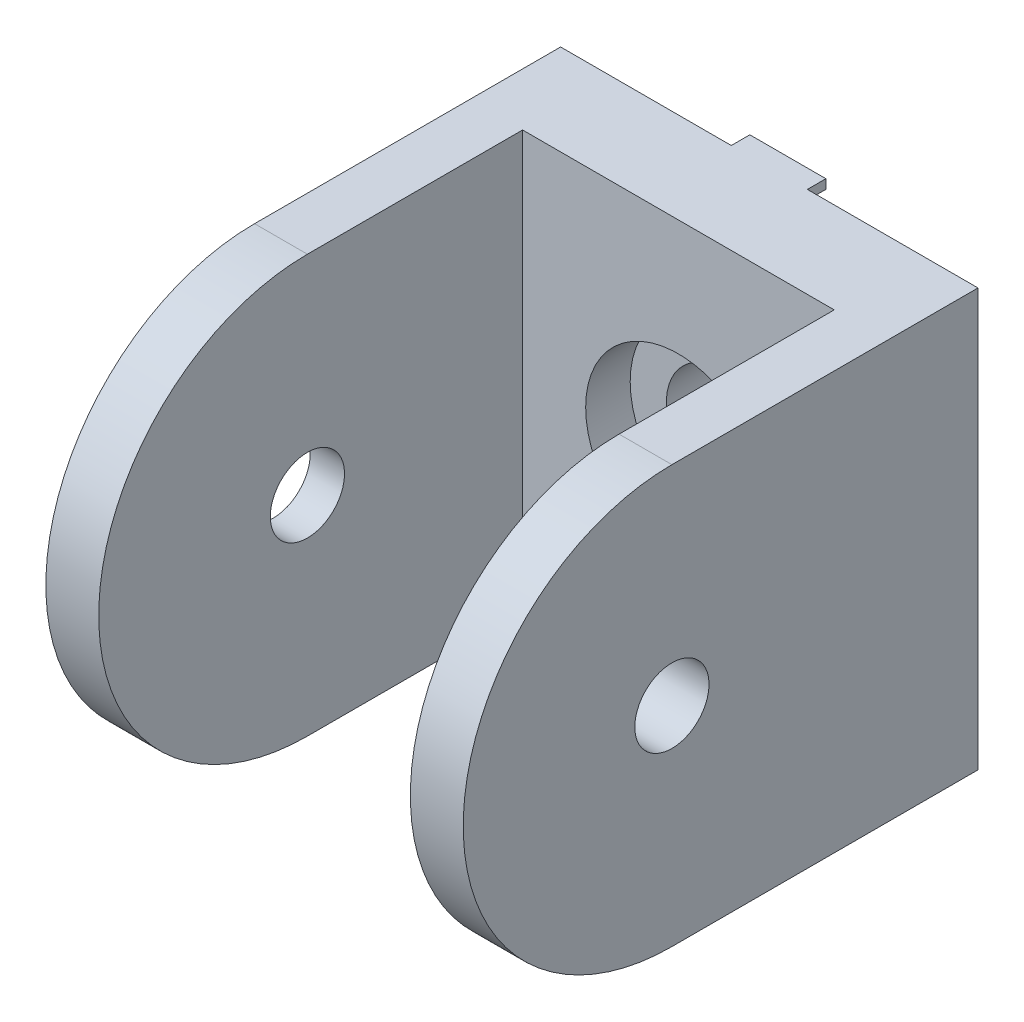
SolidWorks part; units mm, degrees
ref_plane "前视基准面" through (0, 0, 0) normal (0, 0, 1) x (1, 0, 0)
ref_plane "上视基准面" through (0, 0, 0) normal (0, 1, 0) x (1, 0, 0)
ref_plane "右视基准面" through (0, 0, 0) normal (1, 0, 0) x (0, 0, -1)
sketch "草图1" plane through (0, 0, 0) normal (0, 0, 1) x (1, 0, 0)
  line L1 (-22.5, -22.5) -> (22.5, -22.5)
  line L2 (-22.5, -22.5) -> (-22.5, 22.5)
  line L3 (-22.5, 22.5) -> (22.5, 22.5)
  line L4 (22.5, -22.5) -> (22.5, 22.5)
  line L5 (-22.5, -22.5) -> (22.5, 22.5) construction
  line L6 (-22.5, 22.5) -> (22.5, -22.5) construction
  point P0 (0, 0)
  dimension "D1" = 45
  dimension "D2" = 45
extrude "凸台-拉伸1" add sketch "草图1" along normal blind 9.8
sketch "草图2" plane through (0, 0, 9.8) normal (0, 0, 1) x (1, 0, 0)
  line L0 (22.5, 22.5) -> (-22.5, 22.5) construction
  line L1 (-22.5, -22.5) -> (-16.8, -22.5)
  line L2 (-22.5, -22.5) -> (-22.5, 22.5)
  line L3 (-22.5, 22.5) -> (-16.8, 22.5)
  line L4 (-16.8, -22.5) -> (-16.8, 22.5)
  line L5 (0, 0) -> (0, 12.8397) construction
  line L6 (22.5, -22.5) -> (16.8, -22.5)
  line L7 (22.5, -22.5) -> (22.5, 22.5)
  line L8 (16.8, -22.5) -> (16.8, 22.5)
  line L9 (22.5, 22.5) -> (16.8, 22.5)
  dimension "D1" = 5.7
extrude "凸台-拉伸2" add sketch "草图2" along normal blind 45.7
sketch "草图3" plane through (-22.5, 0, 0) normal (-1, 0, 0) x (0, 0, 1)
  line L0 (55.5, 22.5) -> (55.5, -22.5) construction
  line L1 (55.5, 22.5) -> (0, 22.5) construction
  line L2 (33, -22.5) -> (33, 22.5) construction
  arc A0 (33, -22.5) -> (33, 22.5) centre (33, 0) ccw
  dimension "D1" = 45
extrude "切除-拉伸2" cut sketch "草图3" against normal through all and the other way through all flip side to cut
sketch "草图4" plane through (-22.5, 0, 0) normal (-1, 0, 0) x (0, 0, 1)
  circle A0 centre (33, 0) radius 4
  dimension "D1" = 8
extrude "切除-拉伸3" cut sketch "草图4" against normal through all
sketch "草图5" plane through (-22.5, 0, 0) normal (-1, 0, 0) x (0, 0, 1)
  circle A0 centre (33, 0) radius 8
  dimension "D1" = 16
extrude "切除-拉伸4" cut sketch "草图5" against normal blind 2
sketch "草图6" plane through (0, 0, 9.8) normal (0, 0, 1) x (1, 0, 0)
  circle A0 centre (0, 0) radius 6.1
  dimension "D1" = 12.2
extrude "切除-拉伸5" cut sketch "草图6" against normal through all
sketch "草图7" plane through (0, 0, 0) normal (0, 0, -1) x (-1, 0, 0)
  line L0 (-22.5, 22.5) -> (22.5, 22.5) construction
  line L1 (-4.1, 22.5) -> (4.1, 22.5)
  line L2 (-4.1, 22.5) -> (-4.1, 21.5)
  line L3 (-4.1, 21.5) -> (4.1, 21.5)
  line L4 (4.1, 22.5) -> (4.1, 21.5)
  line L5 (0, 0) -> (-9.0525, 0) construction
  line L6 (4.1, -22.5) -> (4.1, -21.5)
  line L7 (-4.1, -22.5) -> (-4.1, -21.5)
  line L8 (-4.1, -21.5) -> (4.1, -21.5)
  line L9 (-4.1, -22.5) -> (4.1, -22.5)
  point P9 (0, 22.5)
  point P10 (0, 22.5)
  dimension "D1" = 8.2
  dimension "D2" = 1
extrude "凸台-拉伸3" add sketch "草图7" along normal blind 2
sketch "草图8" plane through (0, 0, 9.8) normal (0, 0, 1) x (1, 0, 0)
  circle A0 centre (0, 0) radius 10
extrude "切除-拉伸6" cut sketch "草图8" against normal blind 4.8
